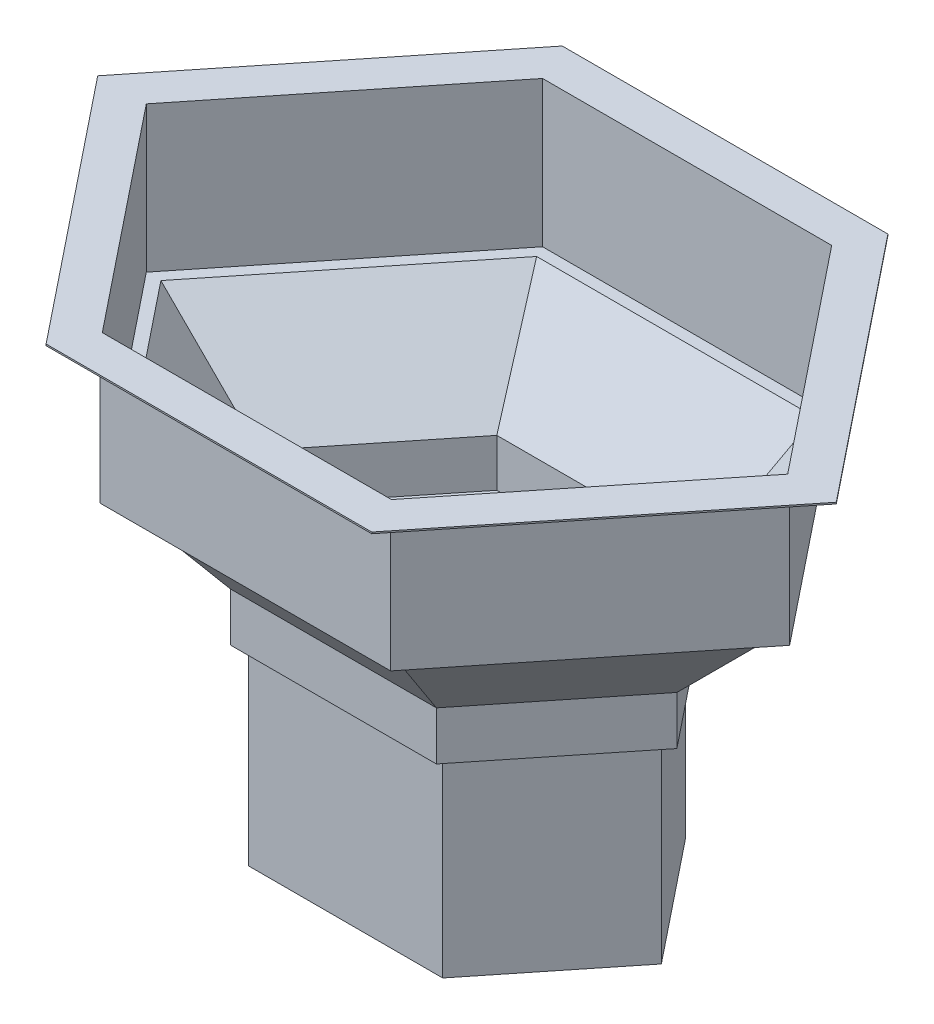
SolidWorks part; units mm, degrees
material "AISI 1020"
ref_plane "Front Plane" through (0, 0, 0) normal (0, 0, 1) x (1, 0, 0)
ref_plane "Top Plane" through (0, 0, 0) normal (0, 1, 0) x (1, 0, 0)
ref_plane "Right Plane" through (0, 0, 0) normal (1, 0, 0) x (0, 0, -1)
sketch "Sketch2" plane through (0, 0, 0) normal (0, 1, 0) x (1, 0, 0)
  line L0 (-203.2, 254) -> (-406.4, 0)
  line L1 (203.2, -254) -> (-203.2, -254)
  line L2 (-406.4, 0) -> (406.4, 0) construction
  line L3 (203.2, 254) -> (-203.2, 254)
  line L4 (-203.2, 254) -> (-203.2, -254) construction
  line L5 (203.2, -254) -> (-203.2, 254) construction
  line L6 (203.2, 254) -> (-203.2, -254) construction
  line L7 (-406.4, 0) -> (-203.2, -254)
  line L8 (203.2, 254) -> (406.4, 0)
  line L9 (406.4, 0) -> (203.2, -254)
  line L10 (203.2, 254) -> (203.2, -254) construction
  point P0 (0, 0)
  dimension "D1" = 406.4
  dimension "D2" = 203.2
  dimension "D3" = 508
extrude "Boss-Extrude1" add sketch "Sketch2" along normal blind 406.4
sketch "Sketch3" plane through (0, 406.4, 0) normal (0, 1, 0) x (1, 0, 0)
  line L0 (215.4079, 279.4) -> (-215.4079, 279.4)
  line L1 (-215.4079, 279.4) -> (-438.9279, 0)
  line L2 (-438.9279, 0) -> (-215.4079, -279.4)
  line L3 (-215.4079, -279.4) -> (215.4079, -279.4)
  line L4 (215.4079, -279.4) -> (438.9279, 0)
  line L5 (438.9279, 0) -> (215.4079, 279.4)
  line L6 (203.2, 254) -> (-203.2, 254)
  line L7 (-203.2, 254) -> (-406.4, 0)
  line L8 (-406.4, 0) -> (-203.2, -254)
  line L9 (-203.2, -254) -> (203.2, -254)
  line L10 (203.2, -254) -> (406.4, 0)
  line L11 (406.4, 0) -> (203.2, 254)
  line L12 (203.2, 254) -> (-203.2, 254) construction
  line L13 (-203.2, 254) -> (-406.4, 0) construction
  line L14 (-406.4, 0) -> (-203.2, -254) construction
  line L15 (-203.2, -254) -> (203.2, -254) construction
  line L16 (203.2, -254) -> (406.4, 0) construction
  line L17 (406.4, 0) -> (203.2, 254) construction
  dimension "D1" = 0
  dimension "D2" = 25.4
extrude "Boss-Extrude2" add sketch "Sketch3" along normal blind 101.6
sketch "Sketch4" plane through (0, 508, 0) normal (0, 1, 0) x (1, 0, 0)
  line L6 (438.9279, 0) -> (215.4079, 279.4)
  line L7 (215.4079, 279.4) -> (-215.4079, 279.4)
  line L8 (-215.4079, 279.4) -> (-438.9279, 0)
  line L9 (-438.9279, 0) -> (-215.4079, -279.4)
  line L10 (-215.4079, -279.4) -> (215.4079, -279.4)
  line L11 (215.4079, -279.4) -> (438.9279, 0)
  line L12 (438.9279, 0) -> (215.4079, 279.4)
  line L13 (215.4079, 279.4) -> (-215.4079, 279.4)
  line L14 (-215.4079, 279.4) -> (-438.9279, 0)
  line L15 (-438.9279, 0) -> (-215.4079, -279.4)
  line L16 (-215.4079, -279.4) -> (215.4079, -279.4)
  line L17 (215.4079, -279.4) -> (438.9279, 0)
  dimension "D1" = 0
ref_plane "Plane1" through (0, 711.2, 0) normal (0, 1, 0) x (1, 0, 0)
sketch "Sketch5" plane through (0, 711.2, 0) normal (0, 1, 0) x (1, 0, 0)
  line L0 (642.1279, 0) -> (291.6698, 438.0725)
  line L1 (291.6698, 438.0725) -> (-291.6698, 438.0725)
  line L2 (-291.6698, 438.0725) -> (-642.1279, 0)
  line L3 (-642.1279, 0) -> (-291.6698, -438.0725)
  line L4 (-291.6698, -438.0725) -> (291.6698, -438.0725)
  line L5 (291.6698, -438.0725) -> (642.1279, 0)
  line L6 (438.9279, 0) -> (215.4079, 279.4)
  line L7 (215.4079, 279.4) -> (-215.4079, 279.4)
  line L8 (-215.4079, 279.4) -> (-438.9279, 0)
  line L9 (-438.9279, 0) -> (-215.4079, -279.4)
  line L10 (-215.4079, -279.4) -> (215.4079, -279.4)
  line L11 (215.4079, -279.4) -> (438.9279, 0)
  line L12 (438.9279, 0) -> (215.4079, 279.4) construction
  line L13 (215.4079, 279.4) -> (-215.4079, 279.4) construction
  line L14 (-215.4079, 279.4) -> (-438.9279, 0) construction
  line L15 (-438.9279, 0) -> (-215.4079, -279.4) construction
  line L16 (-215.4079, -279.4) -> (215.4079, -279.4) construction
  line L17 (215.4079, -279.4) -> (438.9279, 0) construction
  dimension "D2" = 203.2
  dimension "D1" = 0
loft "Loft1" add profiles "Sketch5", "Sketch4" connector at (-642.1279, 711.2, 0) connector at (-438.9279, 508, 0)
sketch "Sketch6" plane through (0, 711.2, 0) normal (0, 1, 0) x (1, 0, 0)
  line L0 (303.8777, -463.4725) -> (674.6557, 0)
  line L1 (674.6557, 0) -> (303.8777, 463.4725)
  line L2 (303.8777, 463.4725) -> (-303.8777, 463.4725)
  line L3 (-303.8777, 463.4725) -> (-674.6557, 0)
  line L4 (-674.6557, 0) -> (-303.8777, -463.4725)
  line L5 (-303.8777, -463.4725) -> (303.8777, -463.4725)
  line L6 (291.6698, -438.0725) -> (642.1279, 0)
  line L7 (642.1279, 0) -> (291.6698, 438.0725)
  line L8 (291.6698, 438.0725) -> (-291.6698, 438.0725)
  line L9 (-291.6698, 438.0725) -> (-642.1279, 0)
  line L10 (-642.1279, 0) -> (-291.6698, -438.0725)
  line L11 (-291.6698, -438.0725) -> (291.6698, -438.0725)
  line L12 (291.6698, -438.0725) -> (642.1279, 0) construction
  line L13 (642.1279, 0) -> (291.6698, 438.0725) construction
  line L14 (291.6698, 438.0725) -> (-291.6698, 438.0725) construction
  line L15 (-291.6698, 438.0725) -> (-642.1279, 0) construction
  line L16 (-642.1279, 0) -> (-291.6698, -438.0725) construction
  line L17 (-291.6698, -438.0725) -> (291.6698, -438.0725) construction
  dimension "D1" = 0
  dimension "D2" = 25.4
extrude "Boss-Extrude3" add sketch "Sketch6" along normal blind 304.8
sketch "Sketch7" plane through (0, 1016, 0) normal (0, 1, 0) x (1, 0, 0)
  line L0 (-340.5013, -539.6725) -> (340.5013, -539.6725)
  line L1 (340.5013, -539.6725) -> (772.2394, 0)
  line L2 (772.2394, 0) -> (340.5013, 539.6725)
  line L3 (340.5013, 539.6725) -> (-340.5013, 539.6725)
  line L4 (-340.5013, 539.6725) -> (-772.2394, 0)
  line L5 (-772.2394, 0) -> (-340.5013, -539.6725)
  line L6 (-303.8777, -463.4725) -> (303.8777, -463.4725)
  line L7 (303.8777, -463.4725) -> (674.6557, 0)
  line L8 (674.6557, 0) -> (303.8777, 463.4725)
  line L9 (303.8777, 463.4725) -> (-303.8777, 463.4725)
  line L10 (-303.8777, 463.4725) -> (-674.6557, 0)
  line L11 (-674.6557, 0) -> (-303.8777, -463.4725)
  line L12 (-303.8777, -463.4725) -> (303.8777, -463.4725) construction
  line L13 (303.8777, -463.4725) -> (674.6557, 0) construction
  line L14 (674.6557, 0) -> (303.8777, 463.4725) construction
  line L15 (303.8777, 463.4725) -> (-303.8777, 463.4725) construction
  line L16 (-303.8777, 463.4725) -> (-674.6557, 0) construction
  line L17 (-674.6557, 0) -> (-303.8777, -463.4725) construction
  dimension "D1" = 0
  dimension "D2" = 76.2
extrude "Boss-Extrude4" add sketch "Sketch7" along normal blind 3.175
shell "Shell3" thickness 3.175 removed face at (0, 1019.175, 0)
